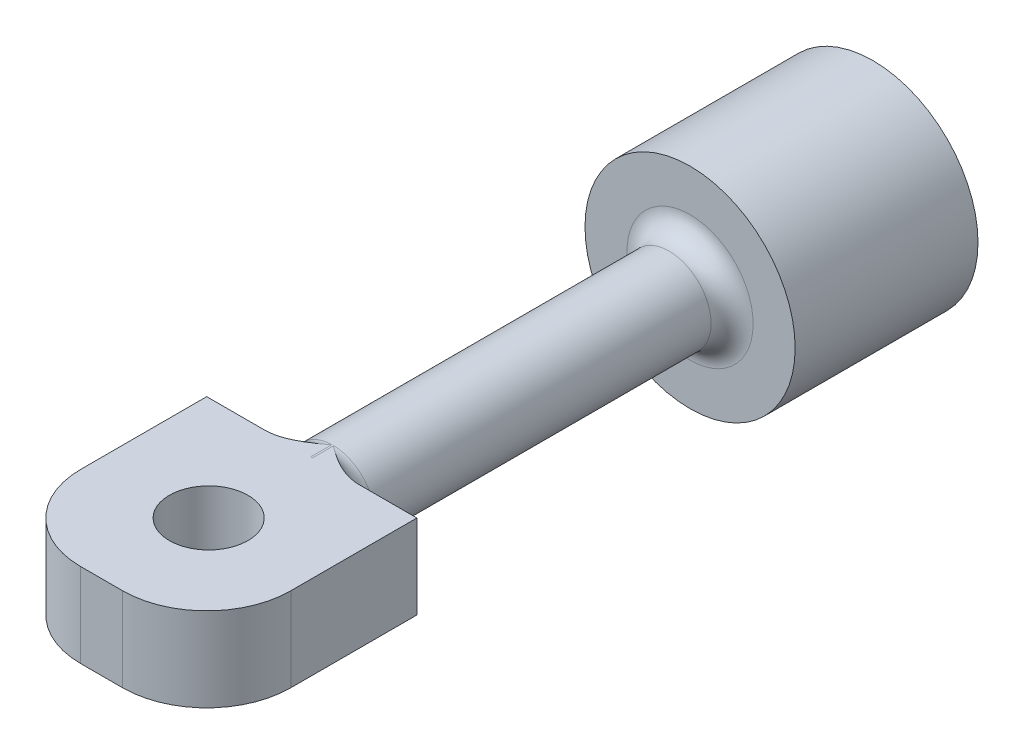
SolidWorks part; units mm, degrees
material "Plain Carbon Steel"
ref_plane "Front Plane" through (0, 0, 0) normal (0, 0, 1) x (1, 0, 0)
ref_plane "Top Plane" through (0, 0, 0) normal (0, 1, 0) x (1, 0, 0)
ref_plane "Right Plane" through (0, 0, 0) normal (1, 0, 0) x (0, 0, -1)
sketch "Sketch1" plane through (0, 0, 0) normal (0, 0, 1) x (1, 0, 0)
  circle A0 centre (-5.6093, 0) radius 6.35
  dimension "D1" = 12.7
extrude "Boss-Extrude1" add sketch "Sketch1" along normal blind 11.049
sketch "Sketch2" plane through (0, 0, 11.049) normal (0, 0, 1) x (1, 0, 0)
  circle A0 centre (-5.6093, 0) radius 2.54
  dimension "D1" = 5.08
extrude "Boss-Extrude2" add sketch "Sketch2" along normal blind 22.86
ref_plane "Plane1" through (0, -16.9545, 16.9545) normal (0, -0.7071, 0.7071) x (1, 0, 0)
sketch "Sketch3" plane through (0, 0, 33.909) normal (0, 0, 1) x (1, 0, 0)
  line L1 (-11.9593, 2.5394) -> (0.7407, 2.5394)
  line L2 (-11.9593, 2.5394) -> (-11.9593, -2.5394)
  line L3 (-11.9593, -2.5394) -> (0.7407, -2.5394)
  line L4 (0.7407, 2.5394) -> (0.7407, -2.5394)
  line L5 (-11.9593, 2.5394) -> (0.7407, -2.5394) construction
  line L6 (-11.9593, -2.5394) -> (0.7407, 2.5394) construction
  point P0 (-5.6093, 0)
  dimension "D1" = 12.7
extrude "Boss-Extrude3" add sketch "Sketch3" along normal blind 12.7
sketch "Sketch4" plane through (0, -2.5394, 0) normal (0, -1, 0) x (1, 0, 0)
  circle A0 centre (-5.5525, 40.1977) radius 2.3749
  dimension "D1" = 4.7498
extrude "Cut-Extrude1" cut sketch "Sketch4" against normal blind 12.7
fillet "Fillet2" radius 5.08 1 edges at (0.7407, 0, 46.609)
fillet "Fillet3" radius 5.08 1 edges at (-11.9593, 0, 46.609)
fillet "Fillet5" radius 1.27 3 edges at (-3.0693, 0, 11.049)
